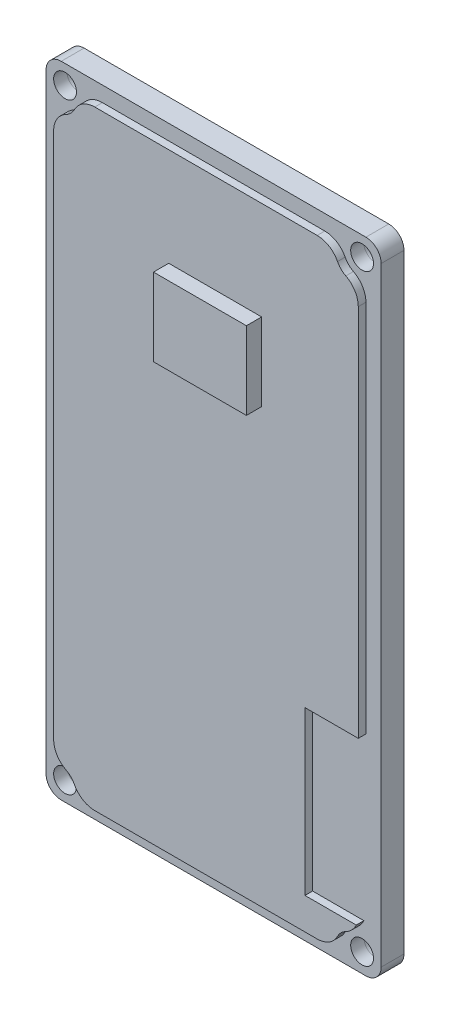
SolidWorks part; units mm, degrees
ref_plane "Front Plane" through (0, 0, 0) normal (0, 0, 1) x (1, 0, 0)
ref_plane "Top Plane" through (0, 0, 0) normal (0, 1, 0) x (1, 0, 0)
ref_plane "Right Plane" through (0, 0, 0) normal (1, 0, 0) x (0, 0, -1)
sketch "baseSketch" plane through (0, 0, 0) normal (0, 0, 1) x (1, 0, 0)
  line L1 (3.8973, 80) -> (33.0994, 80)
  line L2 (-1.5017, 74.601) -> (-1.5017, 5.399)
  line L3 (3.8973, 0) -> (33.0994, 0)
  line L4 (38.4983, 74.601) -> (38.4983, 25.5128)
  line L5 (-1.5017, 82) -> (38.4983, 82)
  line L6 (-3.5017, 80) -> (-3.5017, 0)
  line L7 (-1.5017, -2) -> (38.4983, -2)
  line L8 (40.4983, 80) -> (40.4983, 0)
  line L10 (13.6083, 67.0859) -> (25.8083, 67.0859)
  line L11 (13.6083, 67.0859) -> (13.6083, 56.8861)
  line L12 (13.6083, 56.8861) -> (25.8083, 56.8861)
  line L13 (25.8083, 67.0859) -> (25.8083, 56.8861)
  line L14 (13.6083, 67.0859) -> (25.8083, 56.8861) construction
  line L15 (13.6083, 56.8861) -> (25.8083, 67.0859) construction
  line L17 (25.8083, 67.0859) -> (13.6083, 67.0859) construction
  line L18 (13.6083, 56.8861) -> (25.8083, 56.8861) construction
  line L19 (13.6083, 56.9861) -> (13.6083, 66.9859) construction
  line L20 (31.4983, 25.5128) -> (31.4983, 4.1509)
  line L21 (31.4983, 4.1509) -> (36.4983, 4.1509)
  line L22 (25.8083, 56.9861) -> (25.8083, 66.9859) construction
  line L24 (36.4983, 25.5128) -> (31.4983, 25.5128)
  line L25 (36.4983, 25.5128) -> (38.4983, 25.5128)
  line L27 (38.4983, 4.1509) -> (36.4983, 4.1509)
  line L31 (40.4983, 0) -> (40.4983, 80)
  line L32 (-1.5017, -2) -> (38.4983, -2)
  line L33 (-3.5017, 80) -> (-3.5017, 0)
  line L34 (38.4983, 82) -> (-1.5017, 82)
  line L35 (40.4983, 0) -> (40.4983, 80)
  line L36 (-1.5017, -2) -> (38.4983, -2)
  line L37 (-3.5017, 80) -> (-3.5017, 0)
  line L38 (38.4983, 82) -> (-1.5017, 82)
  arc A4 (38.4983, -2) -> (40.4983, 0) centre (38.4983, 0) ccw
  arc A7 (-3.5017, 0) -> (-1.5017, -2) centre (-1.5017, 0) ccw
  arc A9 (-1.5017, 82) -> (-3.5017, 80) centre (-1.5017, 80) ccw
  arc A11 (38.4983, 82) -> (40.4983, 80) centre (38.4983, 80) cw
  circle A12 centre (-1.0017, 0.5) radius 1.5
  arc A15 (1.2251, 1.6364) -> (0.1347, 2.7268) centre (-1.0017, 0.5) ccw
  circle A16 centre (37.9983, 0.5) radius 1.5
  arc A17 (36.862, 2.7268) -> (35.7715, 1.6364) centre (37.9983, 0.5) ccw
  circle A18 centre (37.9983, 79.5) radius 1.5
  arc A19 (35.7715, 78.3636) -> (36.862, 77.2732) centre (37.9983, 79.5) ccw
  circle A20 centre (-1.0017, 79.5) radius 1.5
  arc A21 (0.1347, 77.2732) -> (1.2251, 78.3636) centre (-1.0017, 79.5) ccw
  arc A22 (35.7715, 78.3636) -> (33.0994, 80) centre (33.0994, 77) ccw construction
  arc A23 (35.7715, 78.3636) -> (33.0994, 80) centre (33.0994, 77) ccw
  arc A26 (38.4983, 74.601) -> (36.862, 77.2732) centre (35.4983, 74.601) ccw construction
  arc A27 (38.4983, 74.601) -> (36.862, 77.2732) centre (35.4983, 74.601) ccw
  arc A28 (33.0994, 0) -> (35.7715, 1.6364) centre (33.0994, 3) ccw construction
  arc A29 (36.862, 2.7268) -> (38.4983, 5.399) centre (35.4983, 5.399) ccw construction
  arc A30 (40.4983, 80) -> (38.4983, 82) centre (38.4983, 80) ccw
  arc A31 (38.4983, -2) -> (40.4983, 0) centre (38.4983, 0) ccw
  arc A32 (-3.5017, 0) -> (-1.5017, -2) centre (-1.5017, 0) ccw
  arc A33 (-1.5017, 82) -> (-3.5017, 80) centre (-1.5017, 80) ccw
  arc A34 (40.4983, 80) -> (38.4983, 82) centre (38.4983, 80) ccw
  arc A35 (38.4983, -2) -> (40.4983, 0) centre (38.4983, 0) ccw
  arc A36 (-3.5017, 0) -> (-1.5017, -2) centre (-1.5017, 0) ccw
  arc A37 (-1.5017, 82) -> (-3.5017, 80) centre (-1.5017, 80) ccw
  arc A38 (1.2251, 1.6364) -> (3.8973, 0) centre (3.8973, 3) ccw construction
  arc A39 (-1.5017, 5.399) -> (0.1347, 2.7268) centre (1.4983, 5.399) ccw construction
  arc A40 (3.8973, 80) -> (1.2251, 78.3636) centre (3.8973, 77) ccw construction
  arc A41 (0.1347, 77.2732) -> (-1.5017, 74.601) centre (1.4983, 74.601) ccw construction
  arc A42 (33.0994, 0) -> (35.7715, 1.6364) centre (33.0994, 3) ccw
  arc A43 (36.862, 2.7268) -> (38.4983, 5.399) centre (35.4983, 5.399) ccw
  arc A44 (1.2251, 1.6364) -> (3.8973, 0) centre (3.8973, 3) ccw
  arc A45 (-1.5017, 5.399) -> (0.1347, 2.7268) centre (1.4983, 5.399) ccw
  arc A46 (3.8973, 80) -> (1.2251, 78.3636) centre (3.8973, 77) ccw
  arc A47 (0.1347, 77.2732) -> (-1.5017, 74.601) centre (1.4983, 74.601) ccw
  point P0 (19.7083, 61.986)
  point P1 (0, 0)
  point P27 (-1.5017, 80)
  point P63 (0, 0)
  point P68 (0, 0)
  dimension "D3" = 0
extrude "base" add sketch "baseSketch" against normal blind 3 contours A20 | A18 | L8 A4 L7 A7 L6 A9 L5 A11 | A16 | A12 region at (37.9983, 79.5, 0) region at (-1.0017, 79.5, 0)
extrude "reverseSkirt" add sketch "baseSketch<6>" along normal blind 1 from surface contours A21 L2 A15 L3 A17 L4 A19 L1 | L13 L10 L11 L12 region at (17.5927, 40.3544, 0) region at (19.7083, 61.986, 0) starting at face at (0.4983, 0.5, 0)
sketch "baseSketch<6>" plane through (0, 0, 0) normal (0, 0, 1) x (1, 0, 0) same geometry as "baseSketch"
extrude "Boss-Extrude3" add sketch "baseSketch<7>" along normal blind 2 from surface contours L13 L10 L11 L12 region at (19.7083, 61.986, 0) starting at face at (20.8916, 36.5286, 1)
sketch "baseSketch<7>" plane through (0, 0, 0) normal (0, 0, 1) x (1, 0, 0) same geometry as "baseSketch"
sketch "TEXT" plane through (0, 0, -3) normal (0, 0, -1) x (-1, 0, 0)
  line L0 (-18.4983, 82) -> (-18.4983, -2) construction
  line L1 (1.5017, 82) -> (-38.4983, 82) construction
  line L2 (1.5017, -2) -> (-38.4983, -2) construction
  text T0 "<b>DRS - C</b>" font "Century Gothic" height 12.7
extrude "Cut-Extrude1" cut sketch "TEXT" against normal blind 0.1 from surface starting at face at (0.4983, 0.5, -3)
fillet "Fillet1" radius 1.27 4 edges at (39.4983, 0.5, -3) (39.4983, 79.5, -3) (0.4983, 0.5, -3) (0.4983, 79.5, -3) second distance 0.254 first distance on face at (39.4983, 0.5, -3) first distance on face at (39.4983, 79.5, -3) first distance on face at (0.4983, 0.5, -3) first distance on face at (0.4983, 79.5, -3)
